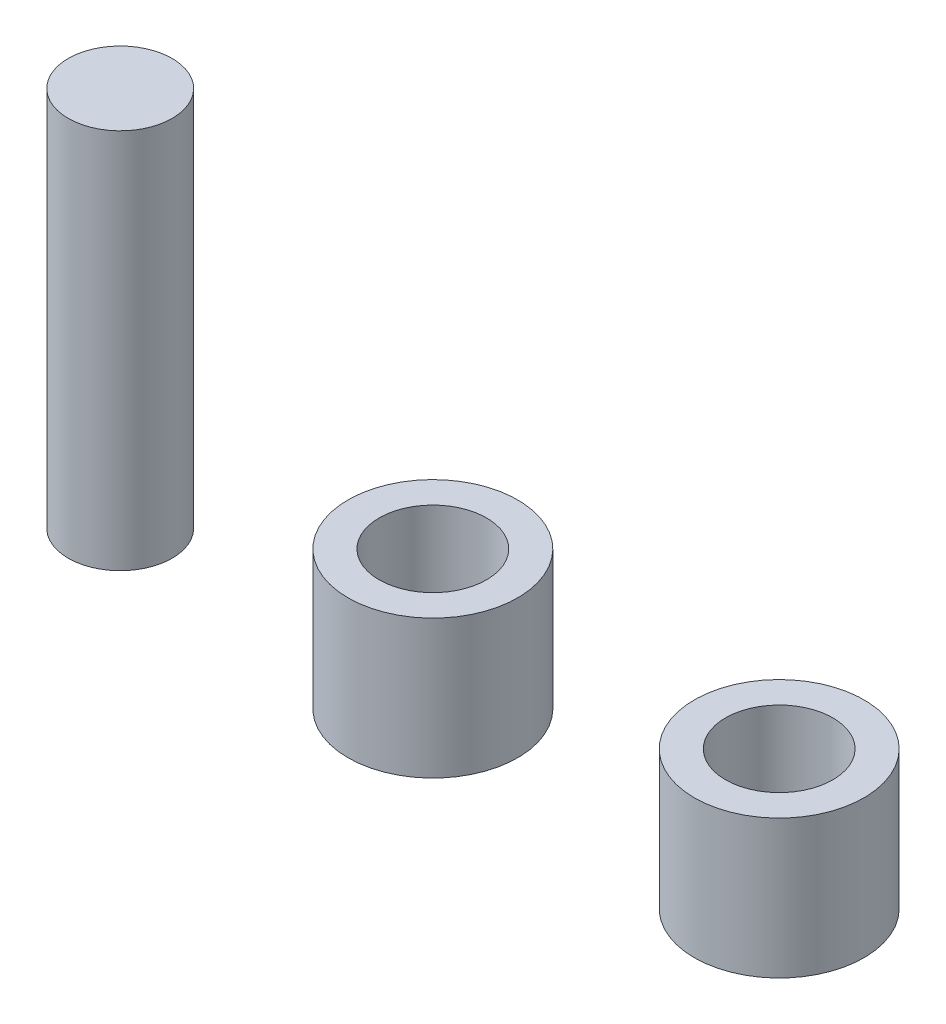
SolidWorks part; units mm, degrees
ref_plane "Front Plane" through (0, 0, 0) normal (0, 0, 1) x (1, 0, 0)
ref_plane "Top Plane" through (0, 0, 0) normal (0, 1, 0) x (1, 0, 0)
ref_plane "Right Plane" through (0, 0, 0) normal (1, 0, 0) x (0, 0, -1)
sketch "Sketch1" plane through (0, 0, 0) normal (0, 1, 0) x (1, 0, 0)
  line L0 (-9.6635, 0) -> (10.2555, 0) construction
  circle A0 centre (0, 0) radius 2.45
  dimension "D1" = 4.9
extrude "Boss-Extrude1" add sketch "Sketch1" along normal blind 4
sketch "Sketch2" plane through (0, 0, 0) normal (0, 1, 0) x (1, 0, 0)
  line L0 (-13.1071, 0) -> (16.2343, 0) construction
  circle A0 centre (-9.0273, 0) radius 1.5
  dimension "D1" = 3
extrude "Boss-Extrude2" add sketch "Sketch2" along normal blind 11 separate body contours A0
sketch "Sketch4" plane through (0, 4, 0) normal (0, 1, 0) x (1, 0, 0)
  line L0 (-2.5821, 0) -> (3.9052, 0) construction
  circle A0 centre (0, 0) radius 1.55
  dimension "D1" = 3.1
extrude "Cut-Extrude1" cut sketch "Sketch4" against normal blind 3
ref_plane "Plane1" through (5, 0, 0) normal (1, 0, 0) x (0, 0, -1)
mirror "Mirror1" about plane through (5, 0, 0) normal (1, 0, 0) of bodies 104 101
